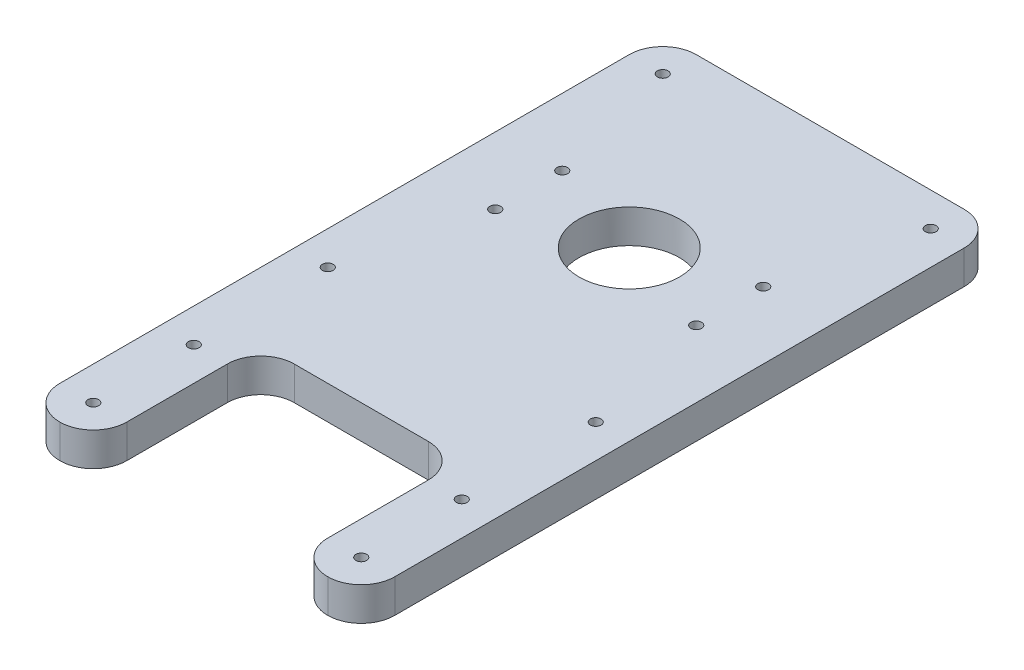
SolidWorks part; units mm, degrees
material "Acrylic (Medium-high impact)"
ref_plane "Front Plane" through (0, 0, 0) normal (0, 0, 1) x (1, 0, 0)
ref_plane "Top Plane" through (0, 0, 0) normal (0, 1, 0) x (1, 0, 0)
ref_plane "Right Plane" through (0, 0, 0) normal (1, 0, 0) x (0, 0, -1)
sketch "Sketch1" plane through (0, 0, 0) normal (0, 1, 0) x (1, 0, 0)
  line L0 (-50, -60) -> (-50, -130)
  line L1 (-50, 60) -> (50, 60)
  line L2 (-50, 60) -> (-50, -60)
  line L3 (-50, -60) -> (50, -60) construction
  line L4 (50, 60) -> (50, -60)
  line L5 (-50, -130) -> (50, -130)
  line L6 (50, -130) -> (50, -60)
  dimension "D1" = 60
  dimension "D2" = 60
  dimension "D3" = 70
  dimension "D4" = 100
  dimension "D5" = 50
extrude "Boss-Extrude1" add sketch "Sketch1" along normal blind 10
sketch "Sketch2" plane through (0, 10, 0) normal (0, 1, 0) x (1, 0, 0)
  line L0 (-40, -120) -> (40, -120) construction
  line L1 (-40, -50) -> (40, -50) construction
  line L2 (-40, -50) -> (-40, 50) construction
  line L3 (-40, 50) -> (40, 50) construction
  line L4 (40, -50) -> (40, 50) construction
  line L5 (-40, -50) -> (40, 50) construction
  line L6 (-40, 50) -> (40, -50) construction
  line L7 (-50, -130) -> (50, -130) construction
  line L8 (0, -50) -> (0, -120) construction
  line L9 (-40, -120) -> (-40, -90) construction
  line L10 (-40, -90) -> (40, -90) construction
  line L11 (40, -90) -> (40, -120) construction
  circle A0 centre (0, 0) radius 15
  circle A1 centre (-40, -50) radius 1.6
  circle A2 centre (40, -50) radius 1.6
  circle A3 centre (40, 50) radius 1.6
  circle A4 centre (-40, 50) radius 1.6
  circle A5 centre (-40, -120) radius 1.6
  circle A6 centre (40, -120) radius 1.6
  circle A7 centre (-40, -90) radius 1.6
  circle A8 centre (40, -90) radius 1.6
  dimension "D1" = 30
  dimension "D2" = 3.2
  dimension "D5" = 10
  dimension "D7" = 30
  dimension "D3" = 100
  dimension "D4" = 80
  dimension "D6" = 80
extrude "Cut-Extrude1" cut sketch "Sketch2" against normal through all both and the other way through all
sketch "Sketch3" plane through (0, 10, 0) normal (0, 1, 0) x (1, 0, 0)
  line L0 (0, 0) -> (0, -105) construction
  line L1 (-30, -130) -> (30, -130)
  line L2 (-30, -130) -> (-30, -80)
  line L3 (-30, -80) -> (30, -80)
  line L4 (30, -130) -> (30, -80)
  line L5 (-30, -130) -> (30, -80) construction
  line L6 (-30, -80) -> (30, -130) construction
  point P0 (0, -105)
  dimension "D1" = 60
  dimension "D2" = 50
  dimension "D3" = 105
extrude "Cut-Extrude2" cut sketch "Sketch3" against normal through all both and the other way through all
sketch "Sketch4" plane through (0, 10, 0) normal (0, 1, 0) x (1, 0, 0)
  line L1 (-30, -10) -> (30, -10) construction
  line L2 (-30, -10) -> (-30, 10) construction
  line L3 (-30, 10) -> (30, 10) construction
  line L4 (30, -10) -> (30, 10) construction
  line L5 (-30, -10) -> (30, 10) construction
  line L6 (-30, 10) -> (30, -10) construction
  circle A0 centre (-30, 10) radius 1.6
  circle A1 centre (-30, -10) radius 1.6
  circle A2 centre (30, 10) radius 1.6
  circle A3 centre (30, -10) radius 1.6
  point P0 (0, 0)
  dimension "D3" = 3.2
  dimension "D1" = 20
  dimension "D2" = 60
extrude "Cut-Extrude3" cut sketch "Sketch4" against normal through all both and the other way through all
fillet "Fillet1" radius 10 8 edges at (50, 5, -60) (-50, 5, -60) (-50, 5, 130) (-30, 5, 130) (50, 5, 130) (30, 5, 130) (30, 5, 80) (-30, 5, 80)
